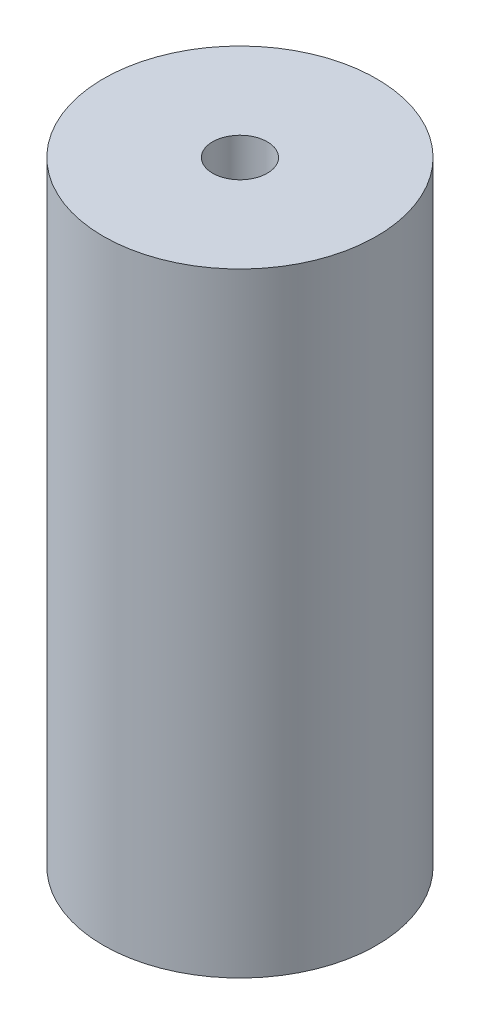
SolidWorks part; units mm, degrees
ref_plane "Front" through (0, 0, 0) normal (0, 0, 1) x (1, 0, 0)
ref_plane "Top" through (0, 0, 0) normal (0, 1, 0) x (1, 0, 0)
ref_plane "Right" through (0, 0, 0) normal (1, 0, 0) x (0, 0, -1)
ref_axis "side-side" through (80.9, 0, 0) along (-1, 0, 0)
ref_axis "up-down" through (0, 50, 0) along (0, -1, 0)
ref_axis "front-back" through (0, 0, -80.9) along (0, 0, 1)
sketch "Sketch1" plane through (0, 0, 0) normal (0, 1, 0) x (1, 0, 0)
  circle A0 centre (0, 0) radius 7.9375
  circle A1 centre (0, 0) radius 1.5875
  dimension "D1" = 15.875
  dimension "D2" = 3.175
extrude "Boss-Extrude1" add sketch "Sketch1" along normal mid plane 35.687
